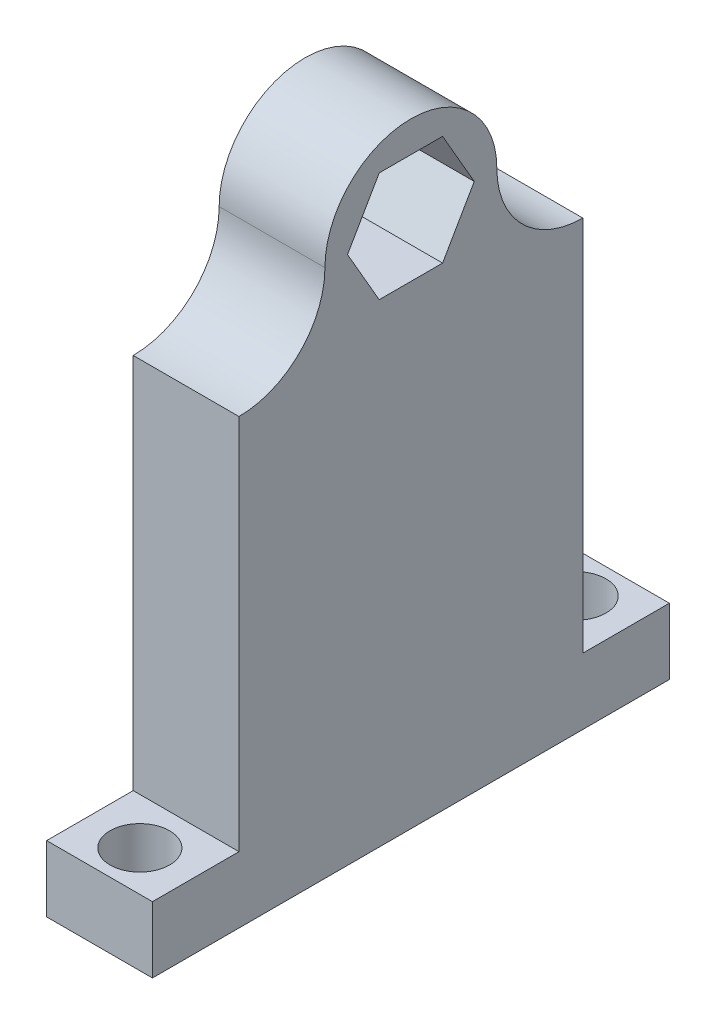
SolidWorks part; units mm, degrees
ref_plane "Спереди" through (0, 0, 0) normal (0, 0, 1) x (1, 0, 0)
ref_plane "Сверху" through (0, 0, 0) normal (0, 1, 0) x (1, 0, 0)
ref_plane "Справа" through (0, 0, 0) normal (1, 0, 0) x (0, 0, -1)
sketch "Эскиз1" plane through (0, 0, 0) normal (1, 0, 0) x (0, 0, -1)
  line L6 (-6.5, 0) -> (6.5, 0) construction
  line L12 (-13, -6.5) -> (-13, -11.5)
  line L13 (13, -6.5) -> (13, -11.5)
  line L15 (-13, -11.5) -> (13, -11.5)
  arc A0 (6.5, 0) -> (-6.5, 0) centre (0, 0) ccw
  arc A1 (-13, -6.5) -> (-6.5, 0) centre (-13, 0) ccw
  arc A2 (6.5, 0) -> (13, -6.5) centre (13, 0) ccw
  point P4 (0, 0)
  point P7 (0, -39.795)
  point P9 (0, 6.5)
  dimension "D1" = 13
  dimension "D4" = 13
  dimension "D5" = 13
  dimension "D2" = 5
extrude "Бобышка-Вытянуть1" add sketch "Эскиз1" along normal blind 8
sketch "Эскиз2" plane through (8, 0, 0) normal (1, 0, 0) x (0, 0, -1)
  line L1 (4.792, 0) -> (2.396, 4.15)
  line L2 (2.396, 4.15) -> (-2.396, 4.15)
  line L3 (-2.396, 4.15) -> (-4.792, 0)
  line L4 (-4.792, 0) -> (-2.396, -4.15)
  line L5 (-2.396, -4.15) -> (2.396, -4.15)
  line L6 (2.396, -4.15) -> (4.792, 0)
  circle A0 centre (0, 0) radius 4.15 construction
  dimension "D1" = 8.3
extrude "Вырез-Вытянуть1" cut sketch "Эскиз2" against normal through all
sketch "Эскиз4" plane through (0, -11.5, 0) normal (0, -1, 0) x (1, 0, 0)
  line L8 (0, 13) -> (0, -13)
  line L9 (0, -13) -> (8, -13)
  line L10 (8, -13) -> (8, 13)
  line L11 (8, 13) -> (0, 13)
  line L12 (0, 13) -> (0, -13)
  line L13 (0, -13) -> (8, -13)
  line L14 (8, -13) -> (8, 13)
  line L15 (8, 13) -> (0, 13)
  dimension "D1" = 0
extrude "Бобышка-Вытянуть2" add sketch "Эскиз4" along normal up to surface (28.5 mm away)
sketch "Эскиз5" plane through (0, -40, 0) normal (0, -1, 0) x (1, 0, 0)
  line L0 (0, 13) -> (0, -13) construction
  line L1 (0, 19.5455) -> (8, 19.5455)
  line L2 (0, 19.5455) -> (0, -19.5455)
  line L3 (0, -19.5455) -> (8, -19.5455)
  line L4 (8, 19.5455) -> (8, -19.5455)
  line L5 (8, -13) -> (8, 13) construction
  line L6 (534, -19.5455) -> (-6, -19.5455) construction
  line L7 (534, 19.5455) -> (-6, 19.5455) construction
  line L8 (4, -16.5) -> (4, 16.5) construction
  line L9 (8, -19.5455) -> (0, 19.5455) construction
  line L10 (0, -19.5455) -> (8, 19.5455) construction
  circle A0 centre (4, -16.5) radius 2.25
  circle A1 centre (4, 16.5) radius 2.25
  point P16 (4, 0)
  point P17 (8, 0)
  point P18 (4, 0)
  dimension "D1" = 4.5
  dimension "D2" = 4.5
  dimension "D3" = 33
extrude "Бобышка-Вытянуть3" add sketch "Эскиз5" against normal blind 5
